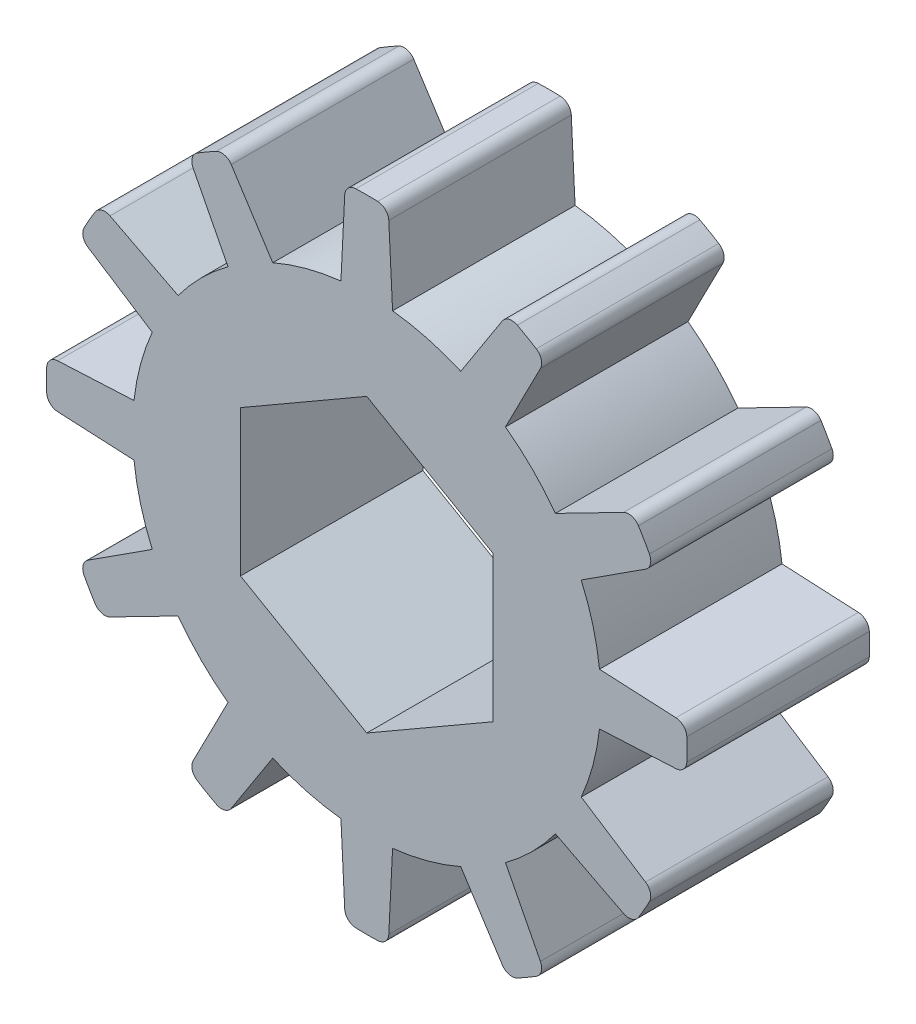
SolidWorks part; units mm, degrees
material "ABS"
ref_plane "Alzado" through (0, 0, 0) normal (0, 0, 1) x (1, 0, 0)
ref_plane "Planta" through (0, 0, 0) normal (0, 1, 0) x (1, 0, 0)
ref_plane "Vista lateral" through (0, 0, 0) normal (1, 0, 0) x (0, 0, -1)
sketch "Croquis1" plane through (0, 0, 0) normal (0, 0, 1) x (1, 0, 0)
  line L0 (0, 0) -> (0, 4.6049) construction
  line L1 (0.375, 5.5679) -> (0.45, 4.0556)
  line L2 (-0.375, 5.5679) -> (-0.45, 4.0556)
  line L3 (2.4592, 5.0094) -> (1.6381, 3.7373)
  line L4 (3.1087, 4.6344) -> (2.4175, 3.2873)
  line L5 (4.6344, 3.1087) -> (3.2873, 2.4175)
  line L6 (5.0094, 2.4592) -> (3.7373, 1.6381)
  line L7 (5.5679, 0.375) -> (4.0556, 0.45)
  line L8 (5.5679, -0.375) -> (4.0556, -0.45)
  line L9 (5.0094, -2.4592) -> (3.7373, -1.6381)
  line L10 (4.6344, -3.1087) -> (3.2873, -2.4175)
  line L11 (3.1087, -4.6344) -> (2.4175, -3.2873)
  line L12 (2.4592, -5.0094) -> (1.6381, -3.7373)
  line L13 (0.375, -5.5679) -> (0.45, -4.0556)
  line L14 (-0.375, -5.5679) -> (-0.45, -4.0556)
  line L15 (-2.4592, -5.0094) -> (-1.6381, -3.7373)
  line L16 (-3.1087, -4.6344) -> (-2.4175, -3.2873)
  line L17 (-4.6344, -3.1087) -> (-3.2873, -2.4175)
  line L18 (-5.0094, -2.4592) -> (-3.7373, -1.6381)
  line L19 (-5.5679, -0.375) -> (-4.0556, -0.45)
  line L20 (-5.5679, 0.375) -> (-4.0556, 0.45)
  line L21 (-5.0094, 2.4592) -> (-3.7373, 1.6381)
  line L22 (-4.6344, 3.1087) -> (-3.2873, 2.4175)
  line L23 (-3.1087, 4.6344) -> (-2.4175, 3.2873)
  line L24 (-2.4592, 5.0094) -> (-1.6381, 3.7373)
  circle A0 centre (0, 0) radius 0.5
  arc A1 (1.6381, 3.7373) -> (0.45, 4.0556) centre (0, 0) ccw
  arc A2 (3.1087, 4.6344) -> (2.4592, 5.0094) centre (0, 0) ccw
  arc A3 (5.0094, 2.4592) -> (4.6344, 3.1087) centre (0, 0) ccw
  arc A4 (5.5679, -0.375) -> (5.5679, 0.375) centre (0, 0) ccw
  arc A5 (4.6344, -3.1087) -> (5.0094, -2.4592) centre (0, 0) ccw
  arc A6 (2.4592, -5.0094) -> (3.1087, -4.6344) centre (0, 0) ccw
  arc A7 (-0.375, -5.5679) -> (0.375, -5.5679) centre (0, 0) ccw
  arc A8 (-3.1087, -4.6344) -> (-2.4592, -5.0094) centre (0, 0) ccw
  arc A9 (-5.0094, -2.4592) -> (-4.6344, -3.1087) centre (0, 0) ccw
  arc A10 (-5.5679, 0.375) -> (-5.5679, -0.375) centre (0, 0) ccw
  arc A11 (-4.6344, 3.1087) -> (-5.0094, 2.4592) centre (0, 0) ccw
  arc A12 (-2.4592, 5.0094) -> (-3.1087, 4.6344) centre (0, 0) ccw
  arc A13 (0.375, 5.5679) -> (-0.375, 5.5679) centre (0, 0) ccw
  arc A14 (3.2873, 2.4175) -> (2.4175, 3.2873) centre (0, 0) ccw
  arc A15 (4.0556, 0.45) -> (3.7373, 1.6381) centre (0, 0) ccw
  arc A16 (3.7373, -1.6381) -> (4.0556, -0.45) centre (0, 0) ccw
  arc A17 (2.4175, -3.2873) -> (3.2873, -2.4175) centre (0, 0) ccw
  arc A18 (0.45, -4.0556) -> (1.6381, -3.7373) centre (0, 0) ccw
  arc A19 (-1.6381, -3.7373) -> (-0.45, -4.0556) centre (0, 0) ccw
  arc A20 (-3.2873, -2.4175) -> (-2.4175, -3.2873) centre (0, 0) ccw
  arc A21 (-4.0556, -0.45) -> (-3.7373, -1.6381) centre (0, 0) ccw
  arc A22 (-3.7373, 1.6381) -> (-4.0556, 0.45) centre (0, 0) ccw
  arc A23 (-2.4175, 3.2873) -> (-3.2873, 2.4175) centre (0, 0) ccw
  arc A24 (-0.45, 4.0556) -> (-1.6381, 3.7373) centre (0, 0) ccw
  dimension "D1" = 0.9
  dimension "D2" = 1
  dimension "D4" = 1.5
  dimension "D3" = 0.75
  dimension "D6" = 1.23
  dimension "D5" = 12
extrude "Saliente-Extruir1" add sketch "Croquis1" along normal blind 3.18
sketch "Croquis10" plane through (0, 0, 0) normal (0, 0, -1) x (-1, 0, 0)
  line L1 (0, -2.5403) -> (2.2, -1.2702)
  line L2 (2.2, -1.2702) -> (2.2, 1.2702)
  line L3 (2.2, 1.2702) -> (0, 2.5403)
  line L4 (0, 2.5403) -> (-2.2, 1.2702)
  line L5 (-2.2, 1.2702) -> (-2.2, -1.2702)
  line L6 (-2.2, -1.2702) -> (0, -2.5403)
  circle A0 centre (0, 0) radius 2.2 construction
  dimension "D1" = 4.4
extrude "Cortar-Extruir3" cut sketch "Croquis10" against normal through all
fillet "Redondeo1" radius 0.2 24 edges at (5.5679, -0.375, 1.59) (-2.4592, -5.0094, 1.59) (-3.1087, -4.6344, 1.59) (0.375, -5.5679, 1.59) (-0.375, -5.5679, 1.59) (3.1087, -4.6344, 1.59) (2.4592, -5.0094, 1.59) (5.0094, -2.4592, 1.59) (4.6344, -3.1087, 1.59) (-4.6344, -3.1087, 1.59) (-5.0094, -2.4592, 1.59) (-5.5679, -0.375, 1.59) (-5.5679, 0.375, 1.59) (-5.0094, 2.4592, 1.59) (-4.6344, 3.1087, 1.59) (-3.1087, 4.6344, 1.59) (-2.4592, 5.0094, 1.59) (5.5679, 0.375, 1.59) (5.0094, 2.4592, 1.59) (4.6344, 3.1087, 1.59) (3.1087, 4.6344, 1.59) (2.4592, 5.0094, 1.59) (0.375, 5.5679, 1.59) (-0.375, 5.5679, 1.59)
